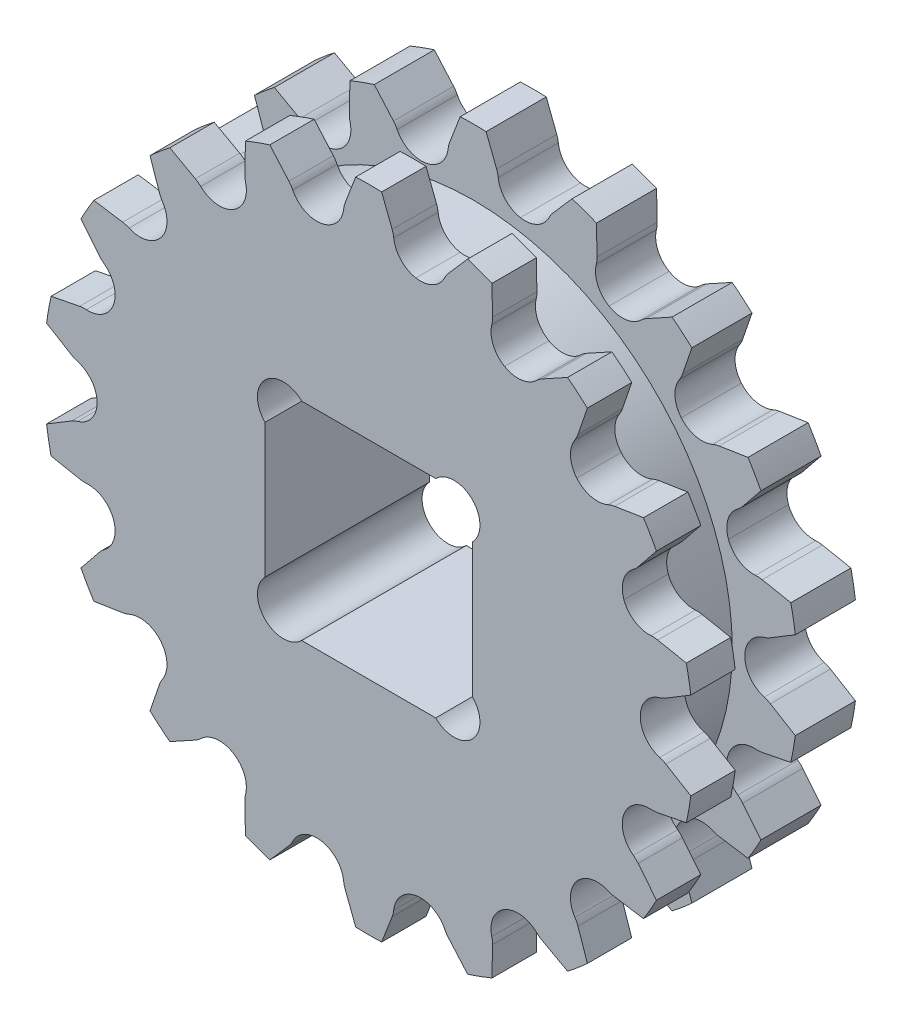
SolidWorks part; units mm, degrees
ref_plane "Front Plane" through (0, 0, 0) normal (0, 0, 1) x (1, 0, 0)
ref_plane "Top Plane" through (0, 0, 0) normal (0, 1, 0) x (1, 0, 0)
ref_plane "Right Plane" through (0, 0, 0) normal (1, 0, 0) x (0, 0, -1)
sketch "Sketch1" plane through (0, 0, 0) normal (0, 0, 1) x (1, 0, 0)
  line L0 (0, 19.9136) -> (0, -19.9136) construction
  line L1 (-3.175, 18.0103) -> (3.175, 18.0103) construction
  line L2 (-0.7937, 19.8978) -> (-1.4366, 18.2315)
  line L3 (-3.175, 18.0103) -> (0, 0) construction
  line L4 (0.7937, 19.8978) -> (1.4377, 18.2314)
  line L5 (3.175, 18.0103) -> (0, 0) construction
  line L6 (-0.7937, 19.8978) -> (0.7937, 19.8978) construction
  line L8 (6.0596, 18.9693) -> (4.8856, 17.6233)
  line L9 (7.5513, 18.4263) -> (7.5865, 16.6402)
  line L10 (12.182, 15.7528) -> (10.6185, 14.8896)
  line L11 (13.3981, 14.7324) -> (12.8203, 13.0419)
  line L12 (16.8351, 10.6363) -> (15.0706, 10.3599)
  line L13 (17.6289, 9.2615) -> (16.5077, 7.8706)
  line L14 (19.4576, 4.2369) -> (17.705, 4.5806)
  line L15 (19.7333, 2.6735) -> (18.2041, 1.75)
  line L16 (19.7333, -2.6735) -> (18.204, -1.7511)
  line L17 (19.4576, -4.2369) -> (17.7048, -4.5817)
  line L18 (17.6289, -9.2615) -> (16.5072, -7.8716)
  line L19 (16.8351, -10.6363) -> (15.07, -10.3608)
  line L20 (13.3981, -14.7324) -> (12.8195, -13.0427)
  line L21 (12.182, -15.7528) -> (10.6176, -14.8902)
  line L22 (7.5513, -18.4263) -> (7.5855, -16.6407)
  line L23 (6.0596, -18.9693) -> (4.8845, -17.6236)
  line L24 (0.7937, -19.8978) -> (1.4366, -18.2315)
  line L25 (-0.7938, -19.8978) -> (-1.4377, -18.2314)
  line L26 (-6.0596, -18.9693) -> (-4.8856, -17.6233)
  line L27 (-7.5513, -18.4263) -> (-7.5865, -16.6402)
  line L28 (-12.182, -15.7528) -> (-10.6185, -14.8896)
  line L29 (-13.3981, -14.7324) -> (-12.8203, -13.0419)
  line L30 (-16.8351, -10.6363) -> (-15.0706, -10.3599)
  line L31 (-17.6289, -9.2615) -> (-16.5077, -7.8706)
  line L32 (-19.4576, -4.2369) -> (-17.705, -4.5806)
  line L33 (-19.7333, -2.6735) -> (-18.2041, -1.75)
  line L34 (-19.7333, 2.6735) -> (-18.204, 1.7511)
  line L35 (-19.4576, 4.2369) -> (-17.7048, 4.5817)
  line L36 (-17.6289, 9.2615) -> (-16.5072, 7.8716)
  line L37 (-16.8351, 10.6363) -> (-15.07, 10.3608)
  line L38 (-13.3981, 14.7324) -> (-12.8195, 13.0427)
  line L39 (-12.182, 15.7528) -> (-10.6176, 14.8902)
  line L40 (-7.5513, 18.4263) -> (-7.5855, 16.6407)
  line L41 (-6.0596, 18.9693) -> (-4.8845, 17.6236)
  circle A0 centre (0, 0) radius 18.288 construction
  arc A1 (0.7937, 19.8978) -> (-0.7937, 19.8978) centre (0, 0) ccw
  arc A4 (1.4377, 18.2314) -> (1.535, 17.8318) centre (-0.0431, 17.6592) cw
  arc A5 (-1.4366, 18.2315) -> (-1.5337, 17.8318) centre (0.0445, 17.6601) ccw
  arc A6 (-2.8884, 16.3844) -> (-1.5337, 17.8318) centre (-3.175, 18.0103) ccw
  arc A8 (2.8896, 16.3841) -> (4.6576, 17.2809) centre (3.1764, 18.01) ccw
  arc A9 (4.8856, 17.6233) -> (4.6576, 17.2809) centre (6.0819, 16.5798) ccw
  arc A10 (7.5513, 18.4263) -> (6.0596, 18.9693) centre (0, 0) ccw
  arc A11 (7.5865, 16.6402) -> (7.5413, 16.2314) centre (5.9993, 16.6089) cw
  arc A12 (8.319, 14.4078) -> (10.2872, 14.6457) centre (9.1446, 15.8375) ccw
  arc A13 (10.6185, 14.8896) -> (10.2872, 14.6457) centre (11.3858, 13.4998) ccw
  arc A14 (13.3981, 14.7324) -> (12.182, 15.7528) centre (0, 0) ccw
  arc A15 (12.8203, 13.0419) -> (12.6379, 12.6732) centre (11.3181, 13.5554) cw
  arc A16 (12.7451, 10.6936) -> (14.6759, 10.2441) centre (14.0099, 11.7548) ccw
  arc A17 (15.0706, 10.3599) -> (14.6759, 10.2441) centre (15.3163, 8.7915) ccw
  arc A18 (17.6289, 9.2615) -> (16.8351, 10.6363) centre (0, 0) ccw
  arc A19 (16.5077, 7.8706) -> (16.2103, 7.5865) centre (15.2718, 8.8669) cw
  arc A20 (15.6339, 5.6896) -> (17.2945, 4.6068) centre (17.1853, 6.2542) ccw
  arc A21 (17.705, 4.5806) -> (17.2945, 4.6068) centre (17.3995, 3.0228) ccw
  arc A22 (19.7333, 2.6735) -> (19.4576, 4.2369) centre (0, 0) ccw
  arc A23 (18.2041, 1.75) -> (17.8274, 1.5848) centre (17.3834, 3.1089) cw
  arc A24 (16.637, -0.0006) -> (17.8272, -1.5861) centre (18.288, -0.0007) ccw
  arc A25 (18.204, -1.7511) -> (17.8272, -1.5861) centre (17.3841, -3.1105) ccw
  arc A26 (19.4576, -4.2369) -> (19.7333, -2.6735) centre (0, 0) ccw
  arc A27 (17.7048, -4.5817) -> (17.2943, -4.6081) centre (17.3984, -3.0241) cw
  arc A28 (15.6335, -5.6908) -> (16.2096, -7.5877) centre (17.1849, -6.2555) ccw
  arc A29 (16.5072, -7.8716) -> (16.2096, -7.5877) centre (15.2718, -8.8686) ccw
  arc A30 (16.8351, -10.6363) -> (17.6289, -9.2615) centre (0, 0) ccw
  arc A31 (15.07, -10.3608) -> (14.6752, -10.2452) centre (15.3148, -8.7923) cw
  arc A32 (12.7443, -10.6945) -> (12.6369, -12.6741) centre (14.009, -11.7558) ccw
  arc A33 (12.8195, -13.0427) -> (12.6369, -12.6741) centre (11.3176, -13.557) ccw
  arc A34 (12.182, -15.7528) -> (13.3981, -14.7324) centre (0, 0) ccw
  arc A35 (10.6176, -14.8902) -> (10.2861, -14.6466) centre (11.3841, -13.5) cw
  arc A36 (8.318, -14.4084) -> (7.54, -16.2318) centre (9.1434, -15.8382) ccw
  arc A37 (7.5855, -16.6407) -> (7.54, -16.2318) centre (5.9983, -16.6103) ccw
  arc A38 (6.0596, -18.9693) -> (7.5513, -18.4263) centre (0, 0) ccw
  arc A39 (4.8845, -17.6236) -> (4.6564, -17.2814) centre (6.0803, -16.5795) cw
  arc A40 (2.8884, -16.3844) -> (1.5337, -17.8318) centre (3.175, -18.0103) ccw
  arc A41 (1.4366, -18.2315) -> (1.5337, -17.8318) centre (-0.0445, -17.6601) ccw
  arc A42 (-0.7938, -19.8978) -> (0.7937, -19.8978) centre (0, 0) ccw
  arc A43 (-1.4377, -18.2314) -> (-1.535, -17.8318) centre (0.0431, -17.6592) cw
  arc A44 (-2.8896, -16.3841) -> (-4.6576, -17.2809) centre (-3.1764, -18.01) ccw
  arc A45 (-4.8856, -17.6233) -> (-4.6576, -17.2809) centre (-6.0819, -16.5798) ccw
  arc A46 (-7.5513, -18.4263) -> (-6.0596, -18.9693) centre (0, 0) ccw
  arc A47 (-7.5865, -16.6402) -> (-7.5413, -16.2314) centre (-5.9993, -16.6089) cw
  arc A48 (-8.319, -14.4078) -> (-10.2872, -14.6457) centre (-9.1446, -15.8375) ccw
  arc A49 (-10.6185, -14.8896) -> (-10.2872, -14.6457) centre (-11.3858, -13.4998) ccw
  arc A50 (-13.3981, -14.7324) -> (-12.182, -15.7528) centre (0, 0) ccw
  arc A51 (-12.8203, -13.0419) -> (-12.6379, -12.6732) centre (-11.3181, -13.5554) cw
  arc A52 (-12.7451, -10.6936) -> (-14.6759, -10.2441) centre (-14.0099, -11.7548) ccw
  arc A53 (-15.0706, -10.3599) -> (-14.6759, -10.2441) centre (-15.3163, -8.7915) ccw
  arc A54 (-17.6289, -9.2615) -> (-16.8351, -10.6363) centre (0, 0) ccw
  arc A55 (-16.5077, -7.8706) -> (-16.2103, -7.5865) centre (-15.2718, -8.8669) cw
  arc A56 (-15.6339, -5.6896) -> (-17.2945, -4.6068) centre (-17.1853, -6.2542) ccw
  arc A57 (-17.705, -4.5806) -> (-17.2945, -4.6068) centre (-17.3995, -3.0228) ccw
  arc A58 (-19.7333, -2.6735) -> (-19.4576, -4.2369) centre (0, 0) ccw
  arc A59 (-18.2041, -1.75) -> (-17.8274, -1.5848) centre (-17.3834, -3.1089) cw
  arc A60 (-16.637, 0.0006) -> (-17.8272, 1.5861) centre (-18.288, 0.0007) ccw
  arc A61 (-18.204, 1.7511) -> (-17.8272, 1.5861) centre (-17.3841, 3.1105) ccw
  arc A62 (-19.4576, 4.2369) -> (-19.7333, 2.6735) centre (0, 0) ccw
  arc A63 (-17.7048, 4.5817) -> (-17.2943, 4.6081) centre (-17.3984, 3.0241) cw
  arc A64 (-15.6335, 5.6908) -> (-16.2096, 7.5877) centre (-17.1849, 6.2555) ccw
  arc A65 (-16.5072, 7.8716) -> (-16.2096, 7.5877) centre (-15.2718, 8.8686) ccw
  arc A66 (-16.8351, 10.6363) -> (-17.6289, 9.2615) centre (0, 0) ccw
  arc A67 (-15.07, 10.3608) -> (-14.6752, 10.2452) centre (-15.3148, 8.7923) cw
  arc A68 (-12.7443, 10.6945) -> (-12.6369, 12.6741) centre (-14.009, 11.7558) ccw
  arc A69 (-12.8195, 13.0427) -> (-12.6369, 12.6741) centre (-11.3176, 13.557) ccw
  arc A70 (-12.182, 15.7528) -> (-13.3981, 14.7324) centre (0, 0) ccw
  arc A71 (-10.6176, 14.8902) -> (-10.2861, 14.6466) centre (-11.3841, 13.5) cw
  arc A72 (-8.318, 14.4084) -> (-7.54, 16.2318) centre (-9.1434, 15.8382) ccw
  arc A73 (-7.5855, 16.6407) -> (-7.54, 16.2318) centre (-5.9983, 16.6103) ccw
  arc A74 (-6.0596, 18.9693) -> (-7.5513, 18.4263) centre (0, 0) ccw
  arc A75 (-4.8845, 17.6236) -> (-4.6564, 17.2814) centre (-6.0803, 16.5795) cw
  arc A76 (-2.8884, 16.3844) -> (-4.6564, 17.2814) centre (-3.175, 18.0103) cw
  arc A77 (-8.318, 14.4084) -> (-10.2861, 14.6466) centre (-9.1434, 15.8382) cw
  arc A78 (-14.6752, 10.2452) -> (-12.7443, 10.6945) centre (-14.0094, 11.7578) ccw
  arc A79 (-17.2943, 4.6081) -> (-15.6335, 5.6908) centre (-17.186, 6.2572) ccw
  arc A80 (-17.8274, -1.5848) -> (-16.637, 0.0006) centre (-18.2896, 0.0019) ccw
  arc A81 (-16.2103, -7.5865) -> (-15.6339, -5.6896) centre (-17.1873, -6.2536) ccw
  arc A82 (-12.6379, -12.6732) -> (-12.7451, -10.6936) centre (-14.0119, -11.7549) ccw
  arc A83 (-7.5413, -16.2314) -> (-8.319, -14.4078) centre (-9.1464, -15.8383) ccw
  arc A84 (-1.535, -17.8318) -> (-2.8896, -16.3841) centre (-3.1778, -18.0114) ccw
  arc A85 (4.6564, -17.2814) -> (2.8884, -16.3844) centre (3.1741, -18.0121) ccw
  arc A86 (10.2861, -14.6466) -> (8.318, -14.4084) centre (9.1432, -15.8402) ccw
  arc A87 (14.6752, -10.2452) -> (12.7443, -10.6945) centre (14.0094, -11.7578) ccw
  arc A88 (15.6335, -5.6908) -> (17.2943, -4.6081) centre (17.1849, -6.2555) cw
  arc A89 (16.637, -0.0006) -> (17.8274, 1.5848) centre (18.288, -0.0007) cw
  arc A90 (16.2103, 7.5865) -> (15.6339, 5.6896) centre (17.1873, 6.2536) ccw
  arc A91 (12.6379, 12.6732) -> (12.7451, 10.6936) centre (14.0119, 11.7549) ccw
  arc A92 (7.5413, 16.2314) -> (8.319, 14.4078) centre (9.1464, 15.8383) ccw
  arc A93 (1.535, 17.8318) -> (2.8896, 16.3841) centre (3.1778, 18.0114) ccw
  point P13 (0, 18.0103)
  point P18 (0, 19.8978)
  point P191 (0, 0)
  dimension "D1" = 39.8272
  dimension "D2" = 36.576
  dimension "D3" = 1.651
  dimension "D5" = 1.5875
  dimension "D8" = 18
  dimension "D4" = 6.35
  dimension "D6" = 1.5875
  dimension "D7" = 6.35
extrude "Boss-Extrude1" add sketch "Sketch1" along normal blind 2.7178
sketch "Sketch3" plane through (0, 0, 0) normal (0, 0, -1) x (-1, 0, 0)
  circle A0 centre (0, 0) radius 15.875
  dimension "D1" = 31.75
extrude "Boss-Extrude2" add sketch "Sketch3" along normal blind 3.683
extrude "Boss-Extrude3" add sketch "Sketch1<2>" against normal blind 3.683 from surface starting at face at (-15.875, 0, -3.683)
sketch "Sketch1<2>" plane through (0, 0, 0) normal (0, 0, 1) x (1, 0, 0) same geometry as "Sketch1"
sketch "Sketch2" plane through (0, 0, 2.7178) normal (0, 0, 1) x (1, 0, 0)
  line L0 (-5.2275, 5.2275) -> (-6.35, 6.35) construction
  line L1 (-4.1049, 6.35) -> (4.1049, 6.35)
  line L2 (-6.35, 4.1049) -> (-6.35, -4.1049)
  line L3 (-4.1049, -6.35) -> (4.1049, -6.35)
  line L4 (6.35, 4.1049) -> (6.35, -4.1049)
  line L5 (-5.2275, 5.2275) -> (6.35, -6.35) construction
  line L6 (-6.35, -6.35) -> (5.2275, 5.2275) construction
  line L7 (-6.35, 0) -> (6.35, 0) construction
  line L8 (0, 6.35) -> (0, -6.35) construction
  arc A0 (-6.35, 4.1049) -> (-4.1049, 6.35) centre (-5.2275, 5.2275) cw
  arc A1 (6.35, 4.1049) -> (4.1049, 6.35) centre (5.2275, 5.2275) ccw
  arc A2 (6.35, -4.1049) -> (4.1049, -6.35) centre (5.2275, -5.2275) cw
  arc A3 (-6.35, -4.1049) -> (-4.1049, -6.35) centre (-5.2275, -5.2275) ccw
  point P0 (0, 0)
  dimension "D3" = 1.5875
  dimension "D1" = 12.7
  dimension "D2" = 12.7
extrude "Cut-Extrude1" cut sketch "Sketch2" against normal through all
